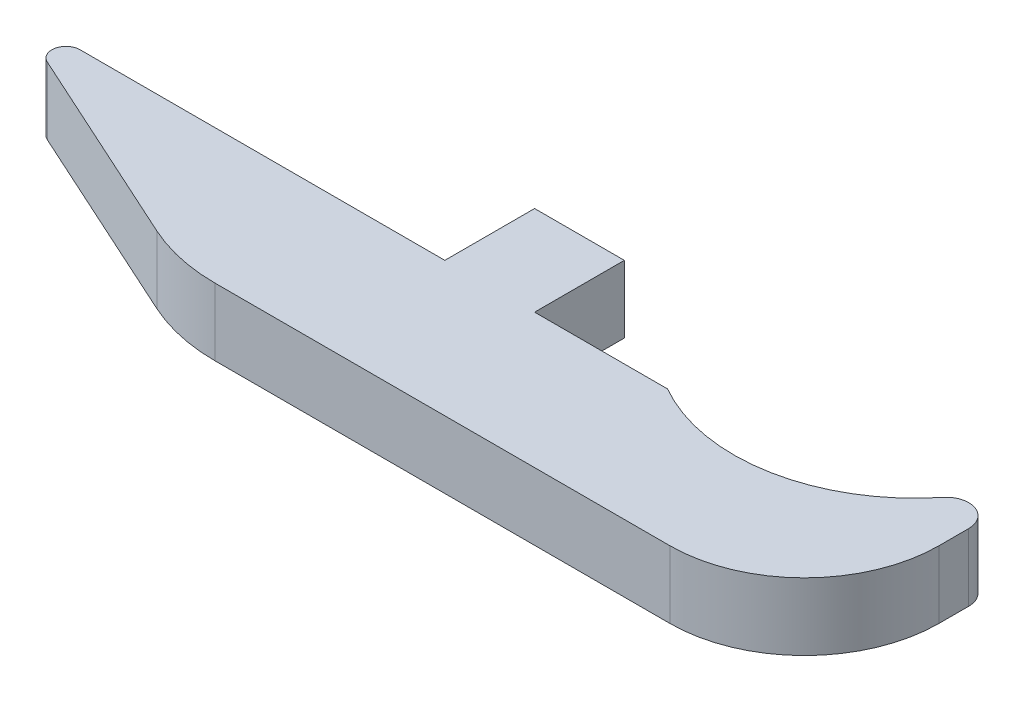
SolidWorks part; units mm, degrees
material "AISI 4130 Steel, annealed at 865C"
ref_plane "X-Y Datum" through (0, 0, 0) normal (0, 0, 1) x (1, 0, 0)
ref_plane "X-Z Datum" through (0, 0, 0) normal (0, 1, 0) x (1, 0, 0)
ref_plane "Y-Z Datum" through (0, 0, 0) normal (1, 0, 0) x (0, 0, -1)
sketch "Sketch1" plane through (0, 0, 0) normal (0, 1, 0) x (1, 0, 0)
  line L0 (20.8895, 0) -> (0, 0) construction
  line L1 (55.7276, 0) -> (0, 0)
  line L2 (55.7276, 0) -> (55.7276, 11.1252)
  line L3 (24.1046, -9.525) -> (68.5546, -9.525)
  line L4 (68.5546, 11.1252) -> (68.5546, -9.525)
  line L5 (3.175, 0) -> (24.1046, -9.525)
  circle A0 centre (55.7276, 11.1252) radius 12.827
  dimension "D3" = 25.654
  dimension "D5" = 9.525
  dimension "D1" = 55.7276
  dimension "D2" = 11.1252
  dimension "D4" = 3.175
  dimension "D6" = 44.45
extrude "Boss-Extrude1" add sketch "Sketch1" along normal blind 4.7625 contours L1 A0 region at (41.3719, 0, 4.2861)
fillet "Fillet1" radius 9.525 1 edges at (68.5546, 2.3813, 9.525)
fillet "Fillet2" radius 1.5875 1 edges at (68.5546, 2.3813, -11.1252)
fillet "Fillet4" radius 12.7 1 edges at (24.1046, 2.3813, 9.525)
sketch "Sketch2" plane through (0, 0, 0) normal (0, -1, 0) x (1, 0, 0)
  line L1 (39.9395, -6.35) -> (39.9395, 0)
  line L2 (-7.0505, -6.35) -> (27.8745, -6.35) construction
  line L3 (39.9395, 0) -> (33.5895, 0)
  line L4 (39.9395, 0) -> (39.9395, -6.35)
  line L5 (39.9395, -6.35) -> (33.5895, -6.35)
  line L6 (33.5895, 0) -> (33.5895, -6.35)
  line L7 (33.5895, 0) -> (33.5895, -6.35) construction
  line M6 (3.175, 0) -> (49.3431, 0)
  dimension "D1" = 6.35
  dimension "D2" = 6.35
extrude "Boss-Extrude2" add sketch "Sketch2" against normal blind 4.7625 contours L6 L5 L1 M6 region at (36.7645, 0, -3.175)
fillet "Fillet5" radius 1 1 edges at (3.175, 2.3813, 0)
